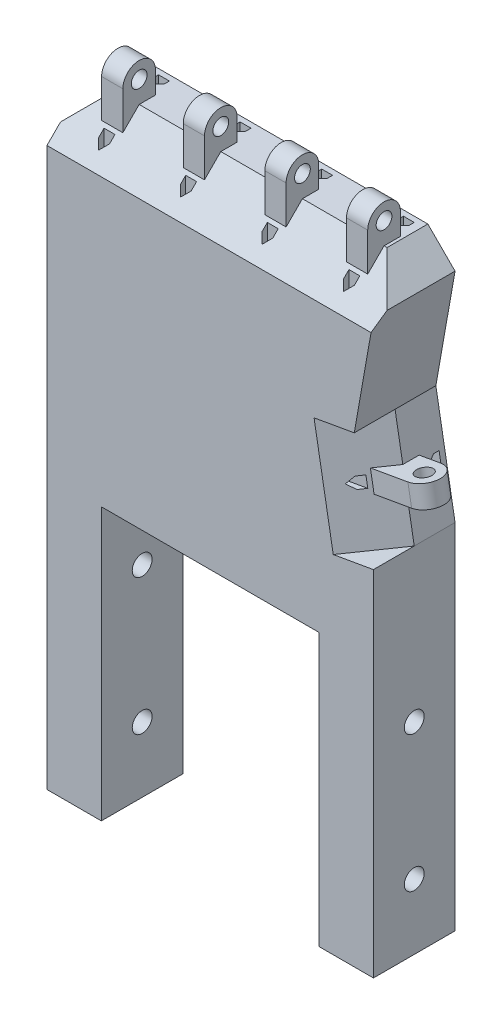
SolidWorks part; units mm, degrees
material "Custom Plastic"
ref_plane "Front Plane" through (0, 0, 0) normal (0, 0, 1) x (1, 0, 0)
ref_plane "Top Plane" through (0, 0, 0) normal (0, 1, 0) x (1, 0, 0)
ref_plane "Right Plane" through (0, 0, 0) normal (1, 0, 0) x (0, 0, -1)
sketch "Sketch1" plane through (0, 0, 0) normal (0, 0, 1) x (1, 0, 0)
  line L1 (-30, -30) -> (30, -30)
  line L2 (-30, -30) -> (-30, 30)
  line L3 (-30, 30) -> (30, 30)
  line L4 (30, -30) -> (30, 30)
  line L5 (-30, -30) -> (30, 30) construction
  line L6 (-30, 30) -> (30, -30) construction
  point P0 (0, 0)
  dimension "D1" = 60
  dimension "D2" = 60
extrude "Boss-Extrude1" add sketch "Sketch1" along normal mid plane 15
sketch "Sketch2" plane through (0, 0, 0) normal (0, 0, 1) x (1, 0, 0)
  line L0 (-30, 25) -> (-25, 30)
  line L1 (-30, 30) -> (-30, -30) construction
  line L2 (30, 30) -> (-30, 30) construction
  line L3 (-25, 30) -> (25, 30)
  line L4 (25, 30) -> (30, 25)
  line L5 (30, -30) -> (30, 30) construction
  line L10 (-30, -30) -> (30, -30) construction
  line L11 (14.5979, -30) -> (-15, -30)
  line L13 (-30, -15) -> (-30, 25)
  line L15 (-30, -15) -> (-30, -30)
  line L16 (-30, -30) -> (-15, -30)
  line L17 (14.5979, -30) -> (30, -30)
  line L18 (30, -30) -> (30, -15)
  line L19 (30, 25) -> (26.4735, 5)
  line L20 (26.4735, 5) -> (30, -15)
  dimension "D1" = 5
  dimension "D2" = 5
  dimension "D3" = 5
  dimension "D4" = 5
  dimension "D5" = 170
  dimension "D6" = 20
  dimension "D7" = 15
extrude "Cut-Extrude6" cut sketch "Sketch2" against normal through all both and the other way through all flip side to cut
ref_plane "Plane1" through (29.5, 0, 0) normal (1, 0, 0) x (0, 0, -1)
sketch "Sketch9" plane through (0, 0, 0) normal (1, 0, 0) x (0, 0, -1)
  line L0 (-7.5, 30) -> (0, 30)
  line L1 (7.5, 30) -> (-7.5, 30) construction
  line L7 (0, 30) -> (-7.5, 22.5)
  line L8 (-7.5, 5) -> (-7.5, 25) construction
  line L9 (-7.5, 22.5) -> (-7.5, 30)
  dimension "D1" = 45
  dimension "D2" = 7.5
extrude "Cut-Extrude7" cut sketch "Sketch9" against normal through all both and the other way through all
sketch "Sketch25" plane through (0, -30, 0) normal (0, -1, 0) x (1, 0, 0)
  line L0 (-30, 7.5) -> (30, 7.5) construction
  line L1 (-30, -7.5) -> (-20, -7.5)
  line L2 (-30, -7.5) -> (-30, 7.5)
  line L3 (-30, 7.5) -> (-20, 7.5)
  line L4 (-20, -7.5) -> (-20, 7.5)
  line L5 (-30, -7.5) -> (-20, 7.5) construction
  line L6 (-30, 7.5) -> (-20, -7.5) construction
  line L8 (0, -8.25) -> (0, 8.25) construction
  line L9 (30, 7.5) -> (20, 7.5)
  line L10 (20, -7.5) -> (20, 7.5)
  line L11 (30, -7.5) -> (20, -7.5)
  line L12 (30, -7.5) -> (30, 7.5)
  point P0 (-25, 0)
  dimension "D1" = 15
  dimension "D2" = 10
  dimension "D3" = 20
extrude "Boss-Extrude5" add sketch "Sketch25" along normal blind 50
sketch "Sketch26" plane through (-20, 0, 0) normal (1, 0, 0) x (0, 0, -1)
  line L5 (7.5, -80) -> (-7.5, -80) construction
  circle A0 centre (0, -68) radius 1.825
  circle A1 centre (0, -43) radius 1.825
  dimension "D1" = 3.65
  dimension "D2" = 3.65
  dimension "D3" = 12
  dimension "D4" = 25
extrude "Cut-Extrude22" cut sketch "Sketch26" against normal through all both and the other way through all
ref_plane "Plane4" through (-22.5, 0, 0) normal (-1, 0, 0) x (0, 0, 1)
ref_plane "Plane5" through (1.7065, -9.678, 0) normal (-0.1736, 0.9848, 0) x (0.9848, 0.1736, 0)
sketch "Sketch31" plane through (1.7065, -9.678, 0) normal (-0.1736, 0.9848, 0) x (0.9848, 0.1736, 0)
  line L0 (26.9395, -7.5) -> (19.4395, -7.5)
  line L1 (19.4395, -7.5) -> (26.9395, 0)
  line L2 (26.9395, 0) -> (26.9395, -7.5)
  line L7 (26.9395, 7.5) -> (26.9395, -7.5) construction
  line L8 (26.9395, -7.5) -> (33.0172, -7.5) construction
  dimension "D1" = 45
  dimension "D2" = 7.5
extrude "Cut-Extrude25" cut sketch "Sketch31" against normal up to vertex (10.1543 mm away) and the other way up to vertex (10.1543 mm away) up to point (30, -15, 7.5) other way up to point (26.4735, 5, -7.5)
sketch "Sketch36" plane through (0, -30, 0) normal (0, -1, 0) x (1, 0, 0)
  line L0 (0, 6.5) -> (-2, 4.5)
  line L1 (-2, 4.5) -> (-2, 2.5)
  line L2 (-2, 2.5) -> (2, 2.5)
  line L3 (2, 2.5) -> (2, 4.5)
  line L4 (2, 4.5) -> (0, 6.5)
  line L5 (-20, 7.5) -> (20, 7.5) construction
  point P8 (0, 7.5)
  dimension "D1" = 2
  dimension "D2" = 135
  dimension "D3" = 2
  dimension "D4" = 135
  dimension "D5" = 4
  dimension "D6" = 1
extrude "Cut-Extrude29" cut sketch "Sketch36" against normal up to surface (30 mm away) up to plane "Top Plane"
pattern_linear "LPattern3" count 2 spacing 9 along (0, 0, -1) of "Cut-Extrude29"
sketch "Sketch41" plane through (0, 30, 0) normal (0, 1, 0) x (1, 0, 0)
  line L0 (-23.5, 6.5) -> (-21.5, 6.5)
  line L1 (-21.5, 6.5) -> (-21.5, 5.5)
  line L2 (-21.5, 5.5) -> (-22.5, 4.5)
  line L3 (-22.5, 8.25) -> (-22.5, -8.25) construction
  line L4 (-22.5, 4.5) -> (-23.5, 5.5)
  line L5 (-23.5, 5.5) -> (-23.5, 6.5)
  line L6 (25, 7.5) -> (-25, 7.5) construction
  line L7 (-8.5, 5.5) -> (-8.5, 6.5)
  line L8 (-8.5, 6.5) -> (-6.5, 6.5)
  line L9 (-6.5, 6.5) -> (-6.5, 5.5)
  line L10 (-6.5, 5.5) -> (-7.5, 4.5)
  line L11 (-7.5, 4.5) -> (-8.5, 5.5)
  line L12 (6.5, 5.5) -> (6.5, 6.5)
  line L13 (6.5, 6.5) -> (8.5, 6.5)
  line L14 (8.5, 6.5) -> (8.5, 5.5)
  line L15 (8.5, 5.5) -> (7.5, 4.5)
  line L16 (7.5, 4.5) -> (6.5, 5.5)
  line L17 (21.5, 5.5) -> (21.5, 6.5)
  line L18 (21.5, 6.5) -> (23.5, 6.5)
  line L19 (23.5, 6.5) -> (23.5, 5.5)
  line L20 (23.5, 5.5) -> (22.5, 4.5)
  line L21 (22.5, 4.5) -> (21.5, 5.5)
  line L22 (-8.5, -4.5) -> (-8.5, -3.5)
  line L23 (-8.5, -3.5) -> (-6.5, -3.5)
  line L24 (-6.5, -3.5) -> (-6.5, -4.5)
  line L25 (-6.5, -4.5) -> (-7.5, -5.5)
  line L26 (-7.5, -5.5) -> (-8.5, -4.5)
  line L27 (6.5, -4.5) -> (6.5, -3.5)
  line L28 (6.5, -3.5) -> (8.5, -3.5)
  line L29 (8.5, -3.5) -> (8.5, -4.5)
  line L30 (8.5, -4.5) -> (7.5, -5.5)
  line L31 (7.5, -5.5) -> (6.5, -4.5)
  line L32 (21.5, -4.5) -> (21.5, -3.5)
  line L33 (21.5, -3.5) -> (23.5, -3.5)
  line L34 (23.5, -3.5) -> (23.5, -4.5)
  line L35 (23.5, -4.5) -> (22.5, -5.5)
  line L36 (22.5, -5.5) -> (21.5, -4.5)
  line L37 (-23.5, -4.5) -> (-23.5, -3.5)
  line L38 (-23.5, -3.5) -> (-21.5, -3.5)
  line L39 (-21.5, -3.5) -> (-21.5, -4.5)
  line L40 (-21.5, -4.5) -> (-22.5, -5.5)
  line L41 (-22.5, -5.5) -> (-23.5, -4.5)
  dimension "D1" = 1
  dimension "D2" = 1
  dimension "D3" = 135
  dimension "D4" = 2
  dimension "D5" = 1
  dimension "D8" = 8
  dimension "D6" = 4
  dimension "D7" = 2
extrude "Cut-Extrude32" cut sketch "Sketch41" against normal blind 7
sketch "Sketch47" plane through (0, 30, 0) normal (0, 1, 0) x (1, 0, 0)
  line L0 (-25, 0) -> (25, 0) construction
  line L1 (-24.45, -3) -> (-20.55, -3)
  line L2 (-24.45, -3) -> (-24.45, 3)
  line L3 (-24.45, 3) -> (-20.55, 3)
  line L4 (-20.55, -3) -> (-20.55, 3)
  line L5 (-24.45, -3) -> (-20.55, 3) construction
  line L6 (-24.45, 3) -> (-20.55, -3) construction
  line L7 (-22.5, 8.25) -> (-22.5, -8.25) construction
  line L8 (-9.45, -3) -> (-9.45, 3)
  line L9 (-9.45, -3) -> (-5.55, -3)
  line L10 (-5.55, -3) -> (-5.55, 3)
  line L11 (-9.45, 3) -> (-5.55, 3)
  line L12 (-9.45, -3) -> (-5.55, 3) construction
  line L13 (-9.45, 3) -> (-5.55, -3) construction
  line L14 (5.55, -3) -> (5.55, 3)
  line L15 (5.55, -3) -> (9.45, -3)
  line L16 (9.45, -3) -> (9.45, 3)
  line L17 (5.55, 3) -> (9.45, 3)
  line L18 (5.55, -3) -> (9.45, 3) construction
  line L19 (5.55, 3) -> (9.45, -3) construction
  line L20 (20.55, -3) -> (20.55, 3)
  line L21 (20.55, -3) -> (24.45, -3)
  line L22 (24.45, -3) -> (24.45, 3)
  line L23 (20.55, 3) -> (24.45, 3)
  line L24 (20.55, -3) -> (24.45, 3) construction
  line L25 (20.55, 3) -> (24.45, -3) construction
  point P0 (-22.5, 0)
  point P11 (-7.5, 0)
  point P16 (7.5, 0)
  point P21 (22.5, 0)
  dimension "D1" = 3.9
  dimension "D2" = 6
  dimension "D3" = 4
extrude "Boss-Extrude6" add sketch "Sketch47" along normal mid plane 8
sketch "Sketch49" plane through (0, 34, 0) normal (0, 1, 0) x (1, 0, 0)
  line L0 (-22.5, 8.25) -> (-22.5, -8.25) construction
  line L1 (-24.45, 0) -> (-20.55, 0)
  line L2 (-24.45, 0) -> (-24.45, 3)
  line L3 (-24.45, 3) -> (-20.55, 3)
  line L4 (-20.55, 0) -> (-20.55, 3)
  line L5 (-24.45, 0) -> (-20.55, 3) construction
  line L6 (-24.45, 3) -> (-20.55, 0) construction
  line L7 (-24.45, 3) -> (-24.45, 0) construction
  point P0 (-22.5, 1.5)
revolve "Revolve2" add sketch "Sketch49" angle 180 about L1
pattern_linear "LPattern7" count 4 spacing 15 along (1, 0, 0) of "Revolve2"
sketch "Sketch50" plane through (-24.45, 0, 0) normal (-1, 0, 0) x (0, 0, 1)
  line L0 (-3, 34) -> (3, 34) construction
  circle A0 centre (0, 34) radius 1.45
  dimension "D1" = 2.9
extrude "Cut-Extrude38" cut sketch "Sketch50" against normal through all both and the other way through all
sketch "Sketch51" plane through (26.5302, 4.678, 0) normal (0.9848, 0.1736, 0) x (0, 0, -1)
  line L0 (3.8203, -9.8273) -> (-3.8203, -9.8273) construction
  line L1 (3, -11.7773) -> (-3, -11.7773)
  line L2 (3, -11.7773) -> (3, -7.8773)
  line L3 (3, -7.8773) -> (-3, -7.8773)
  line L4 (-3, -11.7773) -> (-3, -7.8773)
  line L5 (3, -11.7773) -> (-3, -7.8773) construction
  line L6 (3, -7.8773) -> (-3, -11.7773) construction
  line L8 (0, -19.9816) -> (0, 0.327) construction
  point P0 (0, -9.8273)
  point P7 (0, 0)
  point P11 (0, 0)
  dimension "D1" = 6
  dimension "D2" = 3.9
extrude "Boss-Extrude7" add sketch "Sketch51" along normal mid plane 8
sketch "Sketch52" plane through (30.4695, 5.3726, 0) normal (0.9848, 0.1736, 0) x (0, 0, -1)
  line L0 (3.8203, -9.8273) -> (-3.8203, -9.8273) construction
  line L1 (0, -11.7773) -> (3, -11.7773)
  line L2 (0, -11.7773) -> (0, -7.8773)
  line L3 (0, -7.8773) -> (3, -7.8773)
  line L4 (3, -11.7773) -> (3, -7.8773)
  line L5 (0, -11.7773) -> (3, -7.8773) construction
  line L6 (0, -7.8773) -> (3, -11.7773) construction
  point P0 (1.5, -9.8273)
  point P7 (0, 0)
  point P9 (0, 0)
revolve "Revolve4" add sketch "Sketch52" angle 180 about L2 reverse direction yes
sketch "Sketch53" plane through (1.3679, -7.7576, 0) normal (-0.1736, 0.9848, 0) x (0.9848, 0.1736, 0)
  line L0 (30.9395, 3) -> (30.9395, -3) construction
  arc A0 (30.9395, -3) -> (30.9395, 3) centre (30.9395, 0) ccw construction
  circle A1 centre (30.9395, 0) radius 1.45
  dimension "D1" = 2.9
extrude "Cut-Extrude39" cut sketch "Sketch53" against normal up to surface (3.9 mm away) up to face at (30.151, -6.6425, 0)
ref_plane "Plane3" through (-21.4721, 23.026, 0) normal (0.682, -0.7314, 0) x (0, 0, -1)
sketch "Sketch56" plane through (0, 23, 0) normal (0, 1, 0) x (1, 0, 0)
  line L0 (-22.5, -5.5) -> (-21.5, -4.5)
  line L1 (-21.5, -4.5) -> (-21.5, -3.5)
  line L2 (-21.5, -3.5) -> (-23.5, -3.5)
  line L3 (-23.5, -3.5) -> (-23.5, -4.5)
  line L4 (-23.5, -4.5) -> (-22.5, -5.5)
extrude "Cut-Extrude40" cut sketch "Sketch56" along direction (0.682, -0.7314, 0) on the side against the normal up to surface (23 mm away) up to face at (0, 0, 4.1)
ref_plane "Plane6" through (-6.5879, 22.9748, 0) normal (-0.2756, 0.9613, 0) x (0, 0, -1)
sketch "Sketch57" plane through (0, 23, 0) normal (0, 1, 0) x (1, 0, 0)
  line L0 (-7.5, -5.5) -> (-8.5, -4.5)
  line L1 (-8.5, -4.5) -> (-8.5, -3.5)
  line L2 (-8.5, -3.5) -> (-6.5, -3.5)
  line L3 (-6.5, -3.5) -> (-6.5, -4.5)
  line L4 (-6.5, -4.5) -> (-7.5, -5.5)
extrude "Cut-Extrude41" cut sketch "Sketch57" along direction (-0.2756, 0.9613, 0) on the side against the normal up to surface (23 mm away) up to face at (-0.1413, 0, 4.1217)
mirror "Mirror1" about plane through (0, 0, 0) normal (1, 0, 0) of "Cut-Extrude40", "Cut-Extrude41"
pattern_linear "LPattern8" count 2 spacing 10 along (0, 0, -1) of "Mirror1"
fillet "Fillet1" radius 1 16 edges at (21.5, 23, 4) (6.5, 23, 4) (-6.5, 23, 4) (-21.5, 23, 4) (-23.5, 23, -6) (-21.5, 23, -6) (-6.5, 23, -6) (-8.5, 23, -6) (6.5, 23, -6) (8.5, 23, -6) (21.5, 23, -6) (23.5, 23, -6) (23.5, 23, 4) (8.5, 23, 4) (-8.5, 23, 4) (-23.5, 23, 4)
sketch "Sketch58" plane through (26.5302, 4.678, 0) normal (0.9848, 0.1736, 0) x (0, 0, -1)
  line L0 (6.5, -10.8273) -> (6.5, -8.8273)
  line L1 (6.5, -8.8273) -> (5.5, -8.8273)
  line L2 (5.5, -8.8273) -> (4.5, -9.8273)
  line L3 (4.5, -9.8273) -> (5.5, -10.8273)
  line L4 (5.5, -10.8273) -> (6.5, -10.8273)
  line L6 (3.8203, -9.8273) -> (-3.8203, -9.8273) construction
  line L7 (7.5, -19.9816) -> (7.5, 0.327) construction
  line L8 (-4.5, -10.8273) -> (-3.5, -10.8273)
  line L9 (-3.5, -10.8273) -> (-3.5, -8.8273)
  line L10 (-3.5, -8.8273) -> (-4.5, -8.8273)
  line L11 (-4.5, -8.8273) -> (-5.5, -9.8273)
  line L12 (-5.5, -9.8273) -> (-4.5, -10.8273)
  dimension "D1" = 2
  dimension "D2" = 1
  dimension "D3" = 1
  dimension "D4" = 135
  dimension "D5" = 1
  dimension "D7" = 8
  dimension "D6" = 2
extrude "Cut-Extrude42" cut sketch "Sketch58" against normal blind 29
